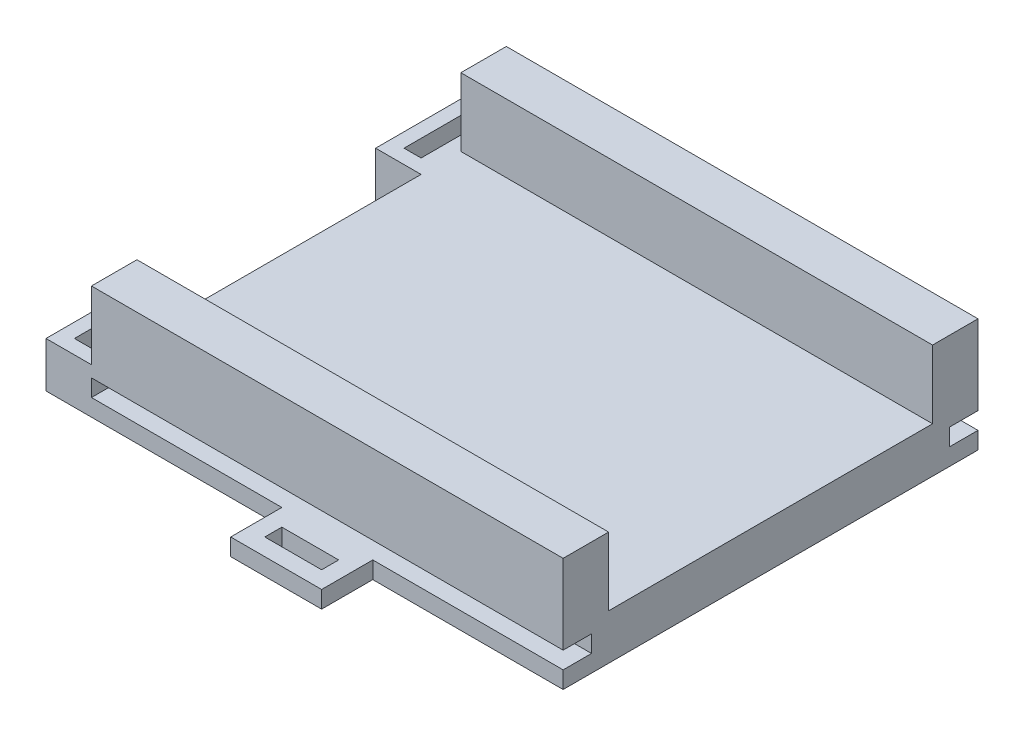
SolidWorks part; units mm, degrees
ref_plane "Front Plane" through (0, 0, 0) normal (0, 0, 1) x (1, 0, 0)
ref_plane "Top Plane" through (0, 0, 0) normal (0, 1, 0) x (1, 0, 0)
ref_plane "Right Plane" through (0, 0, 0) normal (1, 0, 0) x (0, 0, -1)
sketch "Sketch2" plane through (0, 0, 0) normal (1, 0, 0) x (0, 0, -1)
  line L0 (-28.5, 8) -> (28.5, 8)
  line L1 (28.5, 8) -> (28.5, 20)
  line L2 (28.5, 20) -> (36.5, 20)
  line L3 (36.5, 20) -> (36.5, 0)
  line L4 (36.5, 0) -> (-36.5, 0)
  line L5 (28.5, 8) -> (28.5, 0) construction
  line L6 (0, 55) -> (0, -55) construction
  line L7 (-28.5, 8) -> (-28.5, 20)
  line L8 (-28.5, 20) -> (-36.5, 20)
  line L9 (-36.5, 20) -> (-36.5, 0)
  point P4 (0, 8)
  point P16 (0, 0)
  dimension "D1" = 57
  dimension "D2" = 8
  dimension "D3" = 20
extrude "Boss-Extrude1" add sketch "Sketch2" along normal mid plane 83
sketch "Sketch3" plane through (0, 0, 0) normal (0, 1, 0) x (1, 0, 0)
  line L0 (-41.5, 28.5) -> (-41.5, -28.5) construction
  line L1 (-41.5, -21.5) -> (-49.5, -21.5)
  line L2 (-41.5, -21.5) -> (-41.5, -36.5)
  line L3 (-41.5, -36.5) -> (-49.5, -36.5)
  line L4 (-49.5, -21.5) -> (-49.5, -36.5)
  line L5 (-41.5, 36.5) -> (-49.5, 36.5)
  line L6 (-41.5, 36.5) -> (-41.5, 21.5)
  line L7 (-41.5, 21.5) -> (-49.5, 21.5)
  line L8 (-49.5, 36.5) -> (-49.5, 21.5)
  line L9 (-44, -24) -> (-47, -24)
  line L10 (-47, -24) -> (-47, -34)
  line L11 (-44, -34) -> (-47, -34)
  line L12 (-44, -24) -> (-44, -34)
  line L13 (-44, 34) -> (-47, 34)
  line L14 (-47, 34) -> (-47, 24)
  line L15 (-44, 24) -> (-47, 24)
  line L16 (-44, 34) -> (-44, 24)
  line L17 (41.5, -36.5) -> (-41.5, -36.5) construction
  line L18 (-41.5, -28.5) -> (-41.5, -36.5) construction
  line L19 (-5, -39.5) -> (5, -39.5)
  line L20 (-8, -36.5) -> (8, -36.5)
  line L21 (-8, -36.5) -> (-8, -45.5)
  line L22 (-8, -45.5) -> (8, -45.5)
  line L23 (8, -36.5) -> (8, -45.5)
  line L24 (5, -39.5) -> (5, -42.5)
  line L25 (-5, -42.5) -> (5, -42.5)
  line L26 (-5, -39.5) -> (-5, -42.5)
  line L28 (-11, 0) -> (11, 0) construction
  line L29 (-5, 39.5) -> (-5, 42.5)
  line L30 (-5, 42.5) -> (5, 42.5)
  line L31 (5, 39.5) -> (5, 42.5)
  line L32 (8, 36.5) -> (8, 45.5)
  line L33 (-8, 45.5) -> (8, 45.5)
  line L34 (-8, 36.5) -> (-8, 45.5)
  line L35 (-8, 36.5) -> (8, 36.5)
  line L36 (-5, 39.5) -> (5, 39.5)
  point P28 (0, -45.5)
  dimension "D1" = 15
  dimension "D2" = 8
  dimension "D4" = 16
  dimension "D5" = 9
  dimension "D3" = 2.5
  dimension "D6" = 3
extrude "Boss-Extrude2" add sketch "Sketch3" along normal blind 8 contours L1 L4 L3 L2 L9 L12 L11 L10 | L5 L8 L7 L6 L13 L16 L15 L14 region at (-41.67, 0, 29) region at (-41.67, 0, -29)
extrude "Boss-Extrude3" add sketch "Sketch3<3>" along normal blind 3 contours L23 L20 L21 L22 L26 L19 L24 L25 | L34 L35 L32 L33 L36 L29 L30 L31 region at (0, 0, 36.6836) region at (0, 0, -36.6836)
sketch "Sketch3<3>" plane through (0, 0, 0) normal (0, 1, 0) x (1, 0, 0) same geometry as "Sketch3"
sketch "Sketch4" plane through (41.5, 0, 0) normal (1, 0, 0) x (0, 0, -1)
  line L0 (-36.5, 20) -> (-36.5, 0) construction
  line L1 (-36.5, 6) -> (-31.5, 6)
  line L2 (-36.5, 6) -> (-36.5, 3)
  line L3 (-36.5, 3) -> (-31.5, 3)
  line L4 (-31.5, 6) -> (-31.5, 3)
  line L5 (-36.5, 0) -> (36.5, 0) construction
  line L6 (0, 11) -> (0, -11) construction
  line L7 (31.5, 6) -> (31.5, 3)
  line L8 (36.5, 3) -> (31.5, 3)
  line L9 (36.5, 6) -> (36.5, 3)
  line L10 (36.5, 6) -> (31.5, 6)
  point P6 (-34, 3)
  dimension "D1" = 3
  dimension "D2" = 3
  dimension "D3" = 5
extrude "Cut-Extrude1" cut sketch "Sketch4" against normal up to surface (83 mm away) and the other way through all up to face at (-41.5, 14, 32.5)
